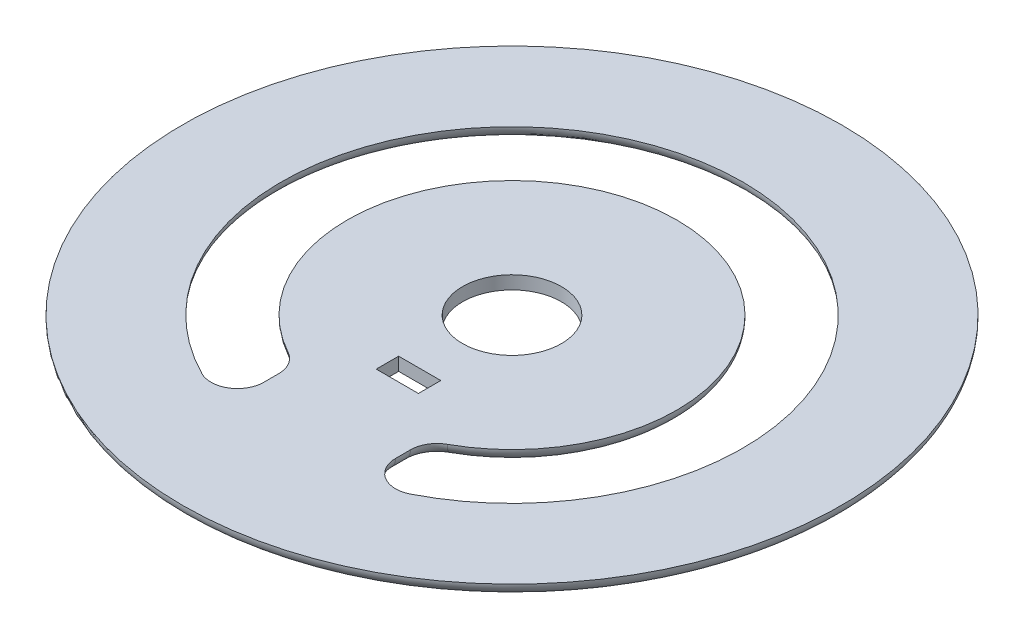
SolidWorks part; units mm, degrees
ref_plane "Front Plane" through (0, 0, 0) normal (0, 0, 1) x (1, 0, 0)
ref_plane "Top Plane" through (0, 0, 0) normal (0, 1, 0) x (1, 0, 0)
ref_plane "Right Plane" through (0, 0, 0) normal (1, 0, 0) x (0, 0, -1)
sketch "Sketch1" plane through (0, 0, 0) normal (0, 1, 0) x (1, 0, 0)
  line L0 (-5, -11.4564) -> (-5, -16.7705)
  line L1 (0, 0) -> (0, -29.6163) construction
  line L2 (5, -11.4564) -> (5, -16.7705)
  line L4 (-1.6, -7) -> (1.6, -7)
  line L5 (-1.6, -7) -> (-1.6, -8.7)
  line L6 (-1.6, -8.7) -> (1.6, -8.7)
  line L7 (1.6, -7) -> (1.6, -8.7)
  arc A0 (5, -11.4564) -> (-5, -11.4564) centre (0, 0) ccw
  circle A1 centre (0, 0) radius 3.75
  arc A2 (5, -16.7705) -> (-5, -16.7705) centre (0, 0) ccw
  circle A3 centre (0, 0) radius 25
  dimension "D1" = 25
  dimension "D2" = 7.5
  dimension "D3" = 35
  dimension "D4" = 50
  dimension "D5" = 5
  dimension "D6" = 1.7
  dimension "D7" = 3.2
  dimension "D8" = 1.6
  dimension "D9" = 7
extrude "Boss-Extrude1" add sketch "Sketch1" along normal blind 1
fillet "Fillet1" radius 2 4 edges at (5, 0.5, 16.7705) (-5, 0.5, 16.7705) (5, 0.5, 11.4564) (-5, 0.5, 11.4564)
fillet "Fillet2" radius 1 9 edges at (5.9527, 0, 15.5332) (5, 0, 13.2639) (5.2779, 0, 11.6813) (0, 0, -12.5) (-5.2779, 0, 11.6813) (-5, 0, 13.2639) (-5.9527, 0, 15.5332) (0, 0, -17.5) (0, 0, 25)
